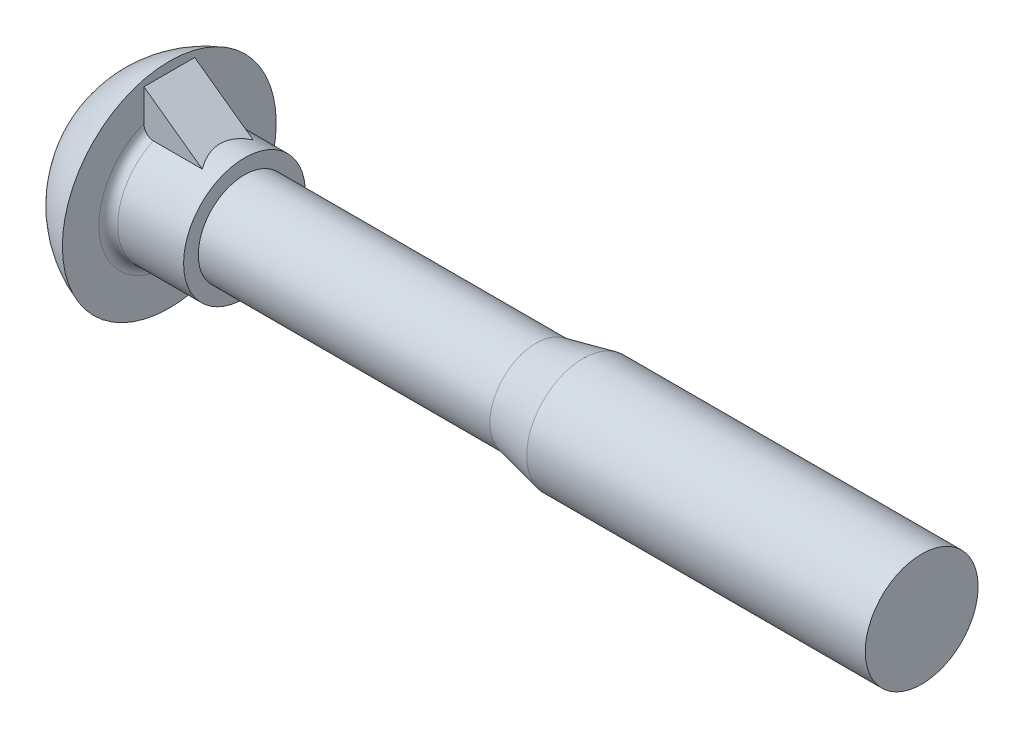
SolidWorks part; units mm, degrees
ref_plane "Front" through (0, 0, 0) normal (0, 0, 1) x (1, 0, 0)
ref_plane "Top" through (0, 0, 0) normal (0, 1, 0) x (1, 0, 0)
ref_plane "Right" through (0, 0, 0) normal (1, 0, 0) x (0, 0, -1)
sketch "Sketch1" plane through (0, 0, 0) normal (0, 0, 1) x (1, 0, 0)
  line L0 (-31.4843, 0) -> (43.5502, 0) construction
  line L1 (44.08, 0) -> (44.08, 3)
  line L2 (44.08, 3) -> (8.08, 3)
  line L3 (8.08, 3) -> (8.08, 3.24)
  line L4 (8.08, 3.24) -> (4.58, 3.24)
  line L5 (4.08, 3.74) -> (4.08, 5.6845)
  line L6 (44.08, 0) -> (0, 0)
  arc A0 (4.08, 5.6845) -> (0, 0) centre (6, 0) ccw
  arc A1 (4.58, 3.24) -> (4.08, 3.74) centre (4.58, 3.74) cw
  point P13 (4.08, 3.24)
revolve "Base" add sketch "Sketch1" angle 360 about L0
cosmetic thread "ThreadCosmetic1" [suppressed] parameters "D2"=4.917
sketch "Sketch2" plane through (0, 0, 0) normal (0, 0, 1) x (1, 0, 0)
  line L1 (6.78, 3.24) -> (4.08, 5.1845)
  line L2 (8.08, 3.24) -> (4.58, 3.24) construction
  line L3 (4.08, -5.6845) -> (4.08, 5.6845) construction
  line L4 (-31.4843, 0) -> (43.5502, 0) construction
rib "Nib" sketch "Sketch2" sketch "Sketch2" thickness 2.7 extrusion direction parallel to sketch draft on no parameters "Sn"=2.7
sketch "Sketch3" plane through (0, 0, 0) normal (0, 0, 1) x (1, 0, 0)
  line L0 (26.08, 3) -> (23.58, 2.4585)
  line L1 (0, 0) -> (55.457, 0) construction
  line L2 (23.58, 2.4585) -> (8.08, 2.4585)
  line L3 (44.08, -3) -> (44.08, 3) construction
  line L4 (8.08, 2.4585) -> (8.08, 3)
  line L5 (8.08, 3) -> (26.08, 3)
  line L6 (-29.8163, 0) -> (1.1759, 0) construction
  dimension "D1" = 4.917
revolve "Cut-Revolve1" cut sketch "Sketch3" angle 360 about L6
sketch "Sketch4" plane through (0, 0, 0) normal (0, 0, 1) x (1, 0, 0)
  line L0 (43.8092, 3.2) -> (44.3507, 3.2)
  line L1 (44.3507, 3.2) -> (44.3507, 3)
  line L2 (44.3507, 3) -> (44.08, 2.531)
  line L3 (44.08, -3) -> (44.08, 3) construction
  line L5 (43.8092, 3) -> (44.08, 2.531)
  line L6 (43.8092, 3.2) -> (43.8092, 3)
  line L8 (44.08, 0) -> (39.6447, 0) construction
  line L9 (43.8092, 3) -> (44.3507, 3) construction
  line L10 (44.08, 3) -> (44.08, 2.531) construction
  point P10 (44.08, 3.2)
  dimension "D2" = 0.5415
  dimension "D3" = 6
revolve "Cut-Revolve10" [suppressed] cut sketch "Sketch4" angle 360 about L8
pattern_linear "LPattern10" [suppressed] count 55 spacing 0.6498 along (-1, 0, 0) of bodies 103
equation "\"D2@Sketch2\" = sqr ( \"r@Sketch1\" * \"r@Sketch1\" -  ( \"r@Sketch1\" - \"k@Sketch1\" )  *  ( \"r@Sketch1\" - \"k@Sketch1\" )  ) -0.5"
equation "\"D2@Sketch4\" =  ( \"d@Sketch1\" - \"D2@ThreadCosmetic1\" )  / 2"
equation "\"D3@LPattern10\" = 1.2 * \"D2@Sketch4\" "
equation "\"D1@LPattern10\" =  ( \"l@Sketch1\" - \"h@Sketch1\" )  /  \"D3@LPattern10\""
equation "\"D1@Sketch3\" = \"D2@ThreadCosmetic1\""
equation "\"D3@Sketch4\" = \"d@Sketch1\""
